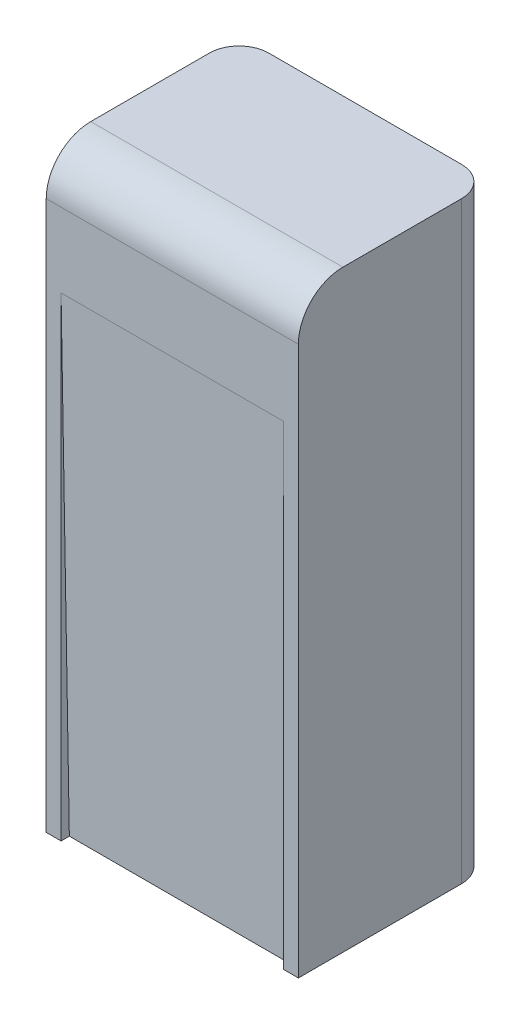
SolidWorks part; units mm, degrees
material "K110"
ref_plane "Front Plane" through (0, 0, 0) normal (0, 0, 1) x (1, 0, 0)
ref_plane "Top Plane" through (0, 0, 0) normal (0, 1, 0) x (1, 0, 0)
ref_plane "Right Plane" through (0, 0, 0) normal (1, 0, 0) x (0, 0, -1)
sketch "Sketch1" plane through (0, 0, 0) normal (0, 1, 0) x (1, 0, 0)
  line L1 (-8.5, -6.5) -> (8.5, -6.5)
  line L2 (-8.5, -6.5) -> (-8.5, 6.5)
  line L3 (-8.5, 6.5) -> (8.5, 6.5)
  line L4 (8.5, -6.5) -> (8.5, 6.5)
  line L5 (-8.5, -6.5) -> (8.5, 6.5) construction
  line L6 (-8.5, 6.5) -> (8.5, -6.5) construction
  point P0 (0, 0)
  dimension "D1" = 13
  dimension "D2" = 17
extrude "Boss-Extrude1" add sketch "Sketch1" against normal blind 40
fillet "Fillet1" radius 2 2 edges at (-8.5, -20, -6.5) (8.5, -20, -6.5)
fillet "Fillet2" radius 3 1 edges at (0, 0, 6.5) tangent propagation no
hole_wizard "M6 Tapped Hole1" positions "Sketch4" profile "Sketch3" tap size "M6" standard "ISO"
sketch "Sketch4" plane through (0, -40, 0) normal (0, -1, 0) x (-1, 0, 0)
  line L0 (-8.5, -6.5) -> (-8.5, 4.5) construction
  line L1 (8.5, 4.5) -> (8.5, -6.5) construction
  point P0 (-1, 0)
  point P2 (1, 0)
  dimension "D1" = 7.5
  dimension "D2" = 7.5
sketch "Sketch3" plane through (1, -40, 0) normal (1, 0, 0) x (0, 0, -1)
  line L0 (0, 0) -> (0, 18.5022)
  line L1 (0, 18.5022) -> (2.5, 17)
  line L2 (2.5, 17) -> (2.5, 0.525)
  line L3 (2.5, 0.525) -> (3.025, 0)
  line L5 (3.025, 0) -> (0, 0)
  line L6 (-2.5, 0.525) -> (-3.025, 0) construction
  line L10 (0, 18.5022) -> (-2.5, 17) construction
  line L11 (0, -6.35) -> (0, 107.95) construction
  dimension "Tap Drill Dia." = 5
  dimension "Tap Drill Depth" = 17
  dimension "Near C'Sink Dia." = 6.05
  dimension "Near C'Sink Angle" = 90
  dimension "Drill Angle" = 118
cosmetic thread "Hole Thread1" parameters "D1"=12, "D2"=6
cosmetic thread "Hole Thread2" parameters "D1"=12, "D2"=6
sketch "Sketch5" plane through (0, 0, 0) normal (1, 0, 0) x (0, 0, -1)
  line L4 (-6.5, -8) -> (-5.9414, -40)
  line L5 (-6.5, -40) -> (-6.5, -3) construction
  line L6 (-6.5, -40) -> (-4.5, -40) construction
  line L7 (-5.9414, -40) -> (-6.5, -40)
  line L8 (-6.5, -40) -> (-6.5, -8)
  dimension "D1" = 5
  dimension "D2" = 1
extrude "Cut-Extrude1" cut sketch "Sketch5" against normal mid plane 15
